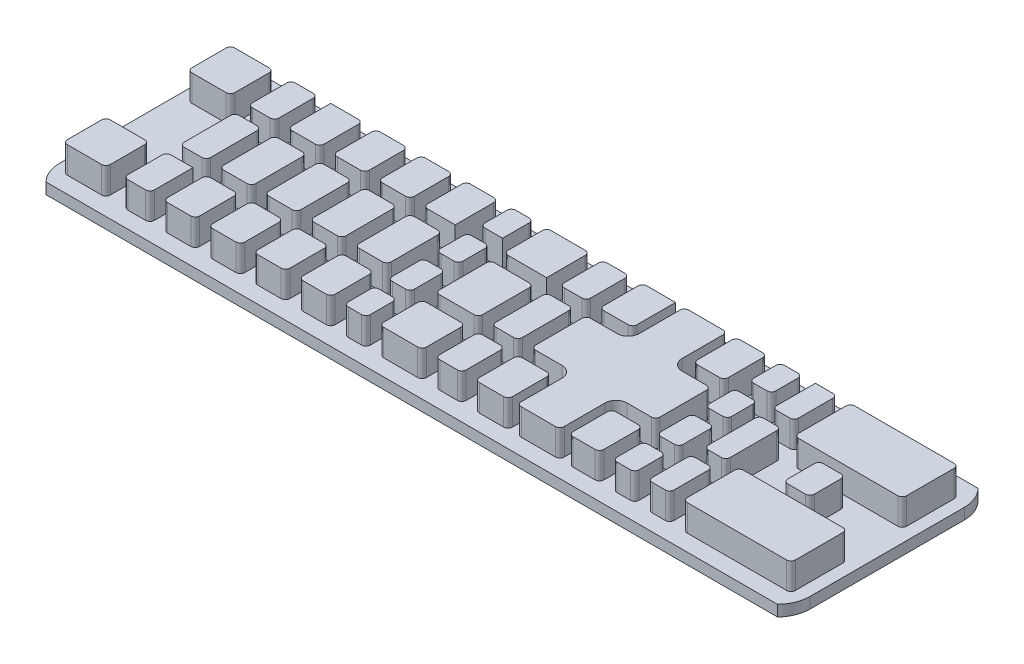
SolidWorks part; units mm, degrees
material "PVB"
ref_plane "Front Plane" through (0, 0, 0) normal (0, 0, 1) x (1, 0, 0)
ref_plane "Top Plane" through (0, 0, 0) normal (0, 1, 0) x (1, 0, 0)
ref_plane "Right Plane" through (0, 0, 0) normal (1, 0, 0) x (0, 0, -1)
ref_axis "X-axis" through (-88.99, 0, 0) along (1, 0, 0)
ref_axis "Y-axis" through (0, 55, 0) along (0, -1, 0)
ref_axis "Z-axis" through (0, 0, -88.99) along (0, 0, 1)
sketch "Sketch1" plane through (0, 0, 0) normal (0, 1, 0) x (1, 0, 0)
  line L1 (109.22, 25.4) -> (-109.22, 25.4)
  line L2 (109.22, 25.4) -> (109.22, -25.4)
  line L3 (109.22, -25.4) -> (-109.22, -25.4)
  line L4 (-109.22, 25.4) -> (-109.22, -25.4)
  line L5 (109.22, 25.4) -> (-109.22, -25.4) construction
  line L6 (109.22, -25.4) -> (-109.22, 25.4) construction
  point P0 (0, 0)
  dimension "D1" = 218.44
  dimension "D2" = 50.8
extrude "Boss-Extrude1" add sketch "Sketch1" along normal blind 2.54
sketch "Sketch4" plane through (0, 2.54, 0) normal (0, 1, 0) x (1, 0, 0)
  line L0 (-99.314, 19.304) -> (-99.314, 9.398)
  line L1 (109.22, 25.4) -> (-109.22, 25.4) construction
  line L2 (-109.22, -25.4) -> (109.22, -25.4) construction
  line L3 (-109.22, 25.4) -> (-109.22, -25.4) construction
  line L4 (-89.408, 19.304) -> (-89.408, 9.398)
  line L5 (-85.344, 19.304) -> (-85.344, 9.398)
  line L6 (-79.248, 19.304) -> (-79.248, 9.398)
  line L7 (-76.2, 19.304) -> (-76.2, 9.398)
  line L8 (-68.834, 19.304) -> (-68.834, 9.398)
  line L9 (-65.786, 19.304) -> (-65.786, 9.398)
  line L10 (-58.42, 19.304) -> (-58.42, 9.398)
  line L11 (-55.372, 19.304) -> (-55.372, 9.398)
  line L12 (-48.006, 19.304) -> (-48.006, 9.398)
  line L13 (-44.958, 19.304) -> (-44.958, 9.398)
  line L14 (-37.592, 19.304) -> (-37.592, 9.398)
  line L15 (-34.544, 19.304) -> (-34.544, 12.192)
  line L16 (35.56, 19.304) -> (35.56, 9.398)
  line L17 (32.512, 19.304) -> (32.512, 12.192)
  line L18 (27.432, 19.304) -> (27.432, 12.192)
  line L19 (24.384, 19.304) -> (24.384, 9.398)
  line L20 (17.272, 19.304) -> (17.272, 9.398)
  line L21 (15.24, 19.304) -> (15.24, 6.35)
  line L22 (5.334, 19.304) -> (5.334, 6.35)
  line L23 (-29.464, 19.304) -> (-29.464, 12.192)
  line L24 (-26.416, 19.304) -> (-26.416, 9.398)
  line L25 (-16.51, 19.304) -> (-16.51, 8.8607)
  line L26 (-13.462, 19.304) -> (-13.462, -6.35)
  line L27 (-7.366, 19.304) -> (-7.366, -6.35)
  line L28 (-4.318, 19.304) -> (-4.318, 9.398)
  line L29 (3.302, 19.304) -> (3.302, 9.398)
  line L30 (-99.314, 19.304) -> (-89.408, 19.304)
  line L31 (-99.314, -19.304) -> (-89.408, -19.304)
  line L32 (-99.314, -9.398) -> (-89.408, -9.398)
  line L33 (-99.314, 9.398) -> (-89.408, 9.398)
  line L34 (-34.544, 9.144) -> (-29.464, 9.144)
  line L35 (-34.544, -9.144) -> (-29.464, -9.144)
  line L36 (-85.344, -19.304) -> (-79.248, -19.304)
  line L37 (-85.344, -9.398) -> (-79.248, -9.398)
  line L38 (-85.344, -6.35) -> (-79.248, -6.35)
  line L39 (-85.344, 9.398) -> (-79.248, 9.398)
  line L40 (-85.344, 6.35) -> (-79.248, 6.35)
  line L41 (-85.344, 19.304) -> (-79.248, 19.304)
  line L42 (-44.958, -19.304) -> (-37.592, -19.304)
  line L43 (-44.958, -9.398) -> (-37.592, -9.398)
  line L44 (-44.958, -6.35) -> (-37.592, -6.35)
  line L45 (-44.958, 6.35) -> (-37.592, 6.35)
  line L46 (-44.958, 9.398) -> (-37.592, 9.398)
  line L47 (-55.372, -19.304) -> (-48.006, -19.304)
  line L48 (-55.372, -9.398) -> (-48.006, -9.398)
  line L49 (-55.372, -6.35) -> (-48.006, -6.35)
  line L50 (-55.372, 6.35) -> (-48.006, 6.35)
  line L51 (-55.372, 9.398) -> (-48.006, 9.398)
  line L52 (-65.786, -19.304) -> (-58.42, -19.304)
  line L53 (-65.786, -9.398) -> (-58.42, -9.398)
  line L54 (-65.786, -6.35) -> (-58.42, -6.35)
  line L55 (-65.786, 6.35) -> (-58.42, 6.35)
  line L56 (-65.786, 9.398) -> (-58.42, 9.398)
  line L57 (-76.2, -19.304) -> (-68.834, -19.304)
  line L58 (-76.2, -9.398) -> (-68.834, -9.398)
  line L59 (-76.2, -6.35) -> (-68.834, -6.35)
  line L60 (-76.2, 6.35) -> (-68.834, 6.35)
  line L61 (-76.2, 9.398) -> (-68.834, 9.398)
  line L62 (-76.2, 19.304) -> (-68.834, 19.304)
  line L63 (-65.786, 19.304) -> (-58.42, 19.304)
  line L64 (-55.372, 19.304) -> (-48.006, 19.304)
  line L65 (-44.958, 19.304) -> (-37.592, 19.304)
  line L66 (-99.314, -9.398) -> (-99.314, -19.304)
  line L67 (-89.408, -9.398) -> (-89.408, -19.304)
  line L68 (-34.544, 12.192) -> (-29.464, 12.192)
  line L69 (-34.544, -1.016) -> (-29.464, -1.016)
  line L70 (-34.544, 2.032) -> (-29.464, 2.032)
  line L71 (-34.544, -12.192) -> (-29.464, -12.192)
  line L72 (-34.544, 19.304) -> (-29.464, 19.304)
  line L73 (-34.544, -19.304) -> (-29.464, -19.304)
  line L74 (-85.344, -9.398) -> (-85.344, -19.304)
  line L75 (-79.248, -9.398) -> (-79.248, -19.304)
  line L76 (-76.2, -9.398) -> (-76.2, -19.304)
  line L77 (-68.834, -9.398) -> (-68.834, -19.304)
  line L78 (-65.786, -9.398) -> (-65.786, -19.304)
  line L79 (-58.42, -9.398) -> (-58.42, -19.304)
  line L80 (-55.372, -9.398) -> (-55.372, -19.304)
  line L81 (-48.006, -9.398) -> (-48.006, -19.304)
  line L82 (-44.958, -9.398) -> (-44.958, -19.304)
  line L83 (-37.592, -9.398) -> (-37.592, -19.304)
  line L84 (-37.592, 6.35) -> (-37.592, -6.35)
  line L85 (-44.958, 6.35) -> (-44.958, -6.35)
  line L86 (-48.006, 6.35) -> (-48.006, -6.35)
  line L87 (-55.372, 6.35) -> (-55.372, -6.35)
  line L88 (-58.42, 6.35) -> (-58.42, -6.35)
  line L89 (-65.786, 6.35) -> (-65.786, -6.35)
  line L90 (-68.834, 6.35) -> (-68.834, -6.35)
  line L91 (-76.2, 6.35) -> (-76.2, -6.35)
  line L92 (-79.248, 6.35) -> (-79.248, -6.35)
  line L93 (-85.344, 6.35) -> (-85.344, -6.35)
  line L94 (-34.544, -12.192) -> (-34.544, -19.304)
  line L95 (-29.464, -12.192) -> (-29.464, -19.304)
  line L96 (-29.464, -1.016) -> (-29.464, -9.144)
  line L97 (-34.544, -1.016) -> (-34.544, -9.144)
  line L98 (-34.544, 9.144) -> (-34.544, 2.032)
  line L99 (-29.464, 9.144) -> (-29.464, 2.032)
  line L100 (-26.416, -19.304) -> (-16.51, -19.304)
  line L101 (-26.416, -9.398) -> (-16.51, -9.398)
  line L102 (-26.416, -6.35) -> (-16.51, -6.35)
  line L103 (-26.416, 6.35) -> (-16.51, 6.35)
  line L104 (-26.416, 9.398) -> (-16.51, 9.398)
  line L105 (-26.416, 19.304) -> (-16.51, 19.304)
  line L106 (-26.416, -9.398) -> (-26.416, -19.304)
  line L107 (-16.51, -9.398) -> (-16.51, -19.304)
  line L108 (-26.416, 6.35) -> (-26.416, -6.35)
  line L109 (-13.462, 19.304) -> (-7.366, 19.304)
  line L110 (-7.366, 19.304) -> (-7.366, 9.398)
  line L111 (-7.366, 9.398) -> (-13.462, 9.398)
  line L112 (-13.462, 9.398) -> (-13.462, 19.304)
  line L113 (-13.462, 6.35) -> (-7.366, 6.35)
  line L114 (-7.366, 6.35) -> (-7.366, -6.35)
  line L115 (-7.366, -6.35) -> (-13.462, -6.35)
  line L116 (-13.462, -6.35) -> (-13.462, 6.35)
  line L117 (-16.51, 6.35) -> (-16.51, -6.35)
  line L118 (-16.51, 9.398) -> (-16.51, 19.304)
  line L119 (-13.462, -9.398) -> (-7.366, -9.398)
  line L120 (-7.366, -9.398) -> (-7.366, -19.304)
  line L121 (-7.366, -19.304) -> (-13.462, -19.304)
  line L122 (-13.462, -19.304) -> (-13.462, -9.398)
  line L123 (-4.318, -19.304) -> (3.302, -19.304)
  line L124 (3.302, -19.304) -> (3.302, -9.398)
  line L125 (3.302, -9.398) -> (-4.318, -9.398)
  line L126 (-4.318, -9.398) -> (-4.318, -19.304)
  line L127 (-4.318, 9.398) -> (3.302, 9.398)
  line L128 (3.302, 9.398) -> (3.302, 19.304)
  line L129 (3.302, 19.304) -> (-4.318, 19.304)
  line L130 (-4.318, 19.304) -> (-4.318, 9.398)
  line L131 (-4.318, 6.35) -> (3.302, 6.35)
  line L132 (-4.318, 6.35) -> (-4.318, -6.35)
  line L133 (-4.318, -6.35) -> (3.302, -6.35)
  line L134 (5.334, -19.304) -> (15.24, -19.304)
  line L135 (15.24, -19.304) -> (15.24, -8.89)
  line L136 (17.78, -6.35) -> (24.384, -6.35)
  line L137 (24.384, -6.35) -> (24.384, 6.35)
  line L138 (24.384, 6.35) -> (17.78, 6.35)
  line L139 (15.24, 8.89) -> (15.24, 19.304)
  line L140 (15.24, 19.304) -> (5.334, 19.304)
  line L141 (5.334, 19.304) -> (5.334, 6.35)
  line L142 (5.334, 6.35) -> (3.302, 6.35)
  line L143 (5.334, -19.304) -> (5.334, -6.35)
  line L144 (5.334, -6.35) -> (3.302, -6.35)
  line L145 (17.272, -19.304) -> (24.384, -19.304)
  line L146 (24.384, -19.304) -> (24.384, -9.398)
  line L147 (24.384, -9.398) -> (17.272, -9.398)
  line L148 (17.272, -9.398) -> (17.272, -19.304)
  line L149 (17.272, 9.398) -> (24.384, 9.398)
  line L150 (24.384, 9.398) -> (24.384, 19.304)
  line L151 (24.384, 19.304) -> (17.272, 19.304)
  line L152 (17.272, 19.304) -> (17.272, 9.398)
  line L153 (40.5638, 19.304) -> (40.5638, 9.398)
  line L154 (43.6118, 19.304) -> (43.6118, 6.35)
  line L155 (35.56, -19.304) -> (40.5638, -19.304)
  line L156 (40.5638, -19.304) -> (40.5638, -9.398)
  line L157 (40.5638, -9.398) -> (35.56, -9.398)
  line L158 (35.56, -9.398) -> (35.56, -19.304)
  line L159 (35.56, -6.35) -> (40.5638, -6.35)
  line L160 (40.5638, -6.35) -> (40.5638, 6.35)
  line L161 (40.5638, 6.35) -> (35.56, 6.35)
  line L162 (35.56, 6.35) -> (35.56, -6.35)
  line L163 (35.56, 19.304) -> (40.5638, 19.304)
  line L164 (40.5638, 19.304) -> (40.5638, 9.398)
  line L165 (40.5638, 9.398) -> (35.56, 9.398)
  line L166 (35.56, 9.398) -> (35.56, 19.304)
  line L167 (27.432, -12.192) -> (32.512, -12.192)
  line L168 (32.512, -12.192) -> (32.512, -19.304)
  line L169 (32.512, -19.304) -> (27.432, -19.304)
  line L170 (27.432, -19.304) -> (27.432, -12.192)
  line L171 (27.432, -9.144) -> (32.512, -9.144)
  line L172 (32.512, -9.144) -> (32.512, -1.016)
  line L173 (32.512, -1.016) -> (27.432, -1.016)
  line L174 (27.432, -1.016) -> (27.432, -9.144)
  line L175 (27.432, 2.032) -> (32.512, 2.032)
  line L176 (32.512, 2.032) -> (32.512, 8.8607)
  line L177 (32.512, 8.8607) -> (27.432, 8.8607)
  line L178 (27.432, 8.8607) -> (27.432, 2.032)
  line L179 (27.432, 12.192) -> (32.512, 12.192)
  line L180 (32.512, 12.192) -> (32.512, 19.304)
  line L181 (32.512, 19.304) -> (27.432, 19.304)
  line L182 (27.432, 19.304) -> (27.432, 12.192)
  line L183 (5.334, -6.35) -> (5.334, -19.304)
  line L184 (3.302, -9.398) -> (3.302, -19.304)
  line L185 (15.24, -6.35) -> (15.24, -19.304)
  line L186 (17.272, -9.398) -> (17.272, -19.304)
  line L187 (-4.318, -9.398) -> (-4.318, -19.304)
  line L188 (-7.366, -9.398) -> (-7.366, -19.304)
  line L189 (-13.462, -9.398) -> (-13.462, -19.304)
  line L190 (-4.318, 6.35) -> (-4.318, -6.35)
  line L191 (24.384, 6.35) -> (24.384, -6.35)
  line L192 (24.384, -9.398) -> (24.384, -19.304)
  line L193 (27.432, 8.8607) -> (27.432, 2.032)
  line L194 (32.512, 8.8607) -> (32.512, 2.032)
  line L195 (27.432, -1.016) -> (27.432, -9.144)
  line L196 (32.512, -1.016) -> (32.512, -9.144)
  line L197 (27.432, -12.192) -> (27.432, -19.304)
  line L198 (32.512, -12.192) -> (32.512, -19.304)
  line L199 (35.56, -9.398) -> (35.56, -19.304)
  line L200 (40.5638, -9.398) -> (40.5638, -19.304)
  line L201 (35.56, 6.35) -> (35.56, -6.35)
  line L202 (40.5638, 6.35) -> (40.5638, -6.35)
  line L203 (43.6118, -19.304) -> (68.5292, -19.304)
  line L205 (43.6118, 19.304) -> (68.5292, 19.304)
  line L206 (68.5292, 6.35) -> (43.6118, 6.35)
  line L207 (43.6118, -6.35) -> (68.5292, -6.35)
  line L208 (51.4858, -3.9841) -> (57.5818, -3.9841)
  line L209 (51.4858, 4.1578) -> (57.5818, 4.1578)
  line L212 (68.5292, 19.304) -> (68.5292, 6.35)
  line L215 (57.5818, 4.1578) -> (57.5818, -3.9841)
  line L216 (51.4858, 4.1578) -> (51.4858, -3.9841)
  line L217 (43.6118, -6.35) -> (43.6118, -19.304)
  line L220 (68.5292, -6.35) -> (68.5292, -19.304)
  arc A0 (17.78, 6.35) -> (15.24, 8.89) centre (17.78, 8.89) cw
  arc A1 (15.24, -8.89) -> (17.78, -6.35) centre (17.78, -8.89) cw
  dimension "D40" = 2.54
  dimension "D41" = 2.54
  dimension "D1" = 9.906
  dimension "D2" = 9.906
  dimension "D3" = 4.064
  dimension "D4" = 6.096
  dimension "D5" = 3.048
  dimension "D6" = 7.366
  dimension "D7" = 3.048
  dimension "D8" = 7.366
  dimension "D9" = 3.048
  dimension "D10" = 7.366
  dimension "D11" = 3.048
  dimension "D12" = 7.366
  dimension "D13" = 3.048
  dimension "D14" = 5.08
  dimension "D15" = 3.048
  dimension "D16" = 9.906
  dimension "D17" = 3.048
  dimension "D18" = 6.096
  dimension "D19" = 3.048
  dimension "D20" = 7.62
  dimension "D21" = 6.096
  dimension "D22" = 6.096
  dimension "D23" = 9.906
  dimension "D24" = 9.906
  dimension "D25" = 7.112
  dimension "D26" = 3.048
  dimension "D27" = 7.112
  dimension "D28" = 3.048
  dimension "D29" = 7.112
  dimension "D30" = 3.048
  dimension "D31" = 2.032
  dimension "D32" = 9.906
  dimension "D33" = 2.032
  dimension "D34" = 7.112
  dimension "D35" = 3.048
  dimension "D36" = 5.08
  dimension "D37" = 3.048
  dimension "D38" = 3.048
  dimension "D39" = 5.0038
  dimension "D42" = 12.954
  dimension "D43" = 12.954
  dimension "D46" = 24.9174
sketch "Sketch5" plane through (0, 2.54, 0) normal (0, 1, 0) x (1, 0, 0)
  line L0 (5.334, 19.304) -> (5.334, 6.35)
  line L1 (-99.314, 9.398) -> (-89.408, 9.398)
  line L2 (-99.314, 9.398) -> (-99.314, 19.304)
  line L3 (-99.314, 19.304) -> (-89.408, 19.304)
  line L4 (-89.408, 9.398) -> (-89.408, 19.304)
  line L5 (-99.314, -19.304) -> (-89.408, -19.304)
  line L6 (-99.314, -19.304) -> (-99.314, -9.398)
  line L7 (-99.314, -9.398) -> (-89.408, -9.398)
  line L8 (-89.408, -19.304) -> (-89.408, -9.398)
  line L9 (-85.344, -19.304) -> (-79.248, -19.304)
  line L10 (-85.344, -19.304) -> (-85.344, -9.398)
  line L11 (-85.344, -9.398) -> (-79.248, -9.398)
  line L12 (-79.248, -19.304) -> (-79.248, -9.398)
  line L13 (-85.344, -6.35) -> (-79.248, -6.35)
  line L14 (-85.344, -6.35) -> (-85.344, 6.35)
  line L15 (-85.344, 6.35) -> (-79.248, 6.35)
  line L16 (-79.248, -6.35) -> (-79.248, 6.35)
  line L17 (-85.344, 9.398) -> (-79.248, 9.398)
  line L18 (-85.344, 9.398) -> (-85.344, 19.304)
  line L19 (-85.344, 19.304) -> (-79.248, 19.304)
  line L20 (-79.248, 9.398) -> (-79.248, 19.304)
  line L21 (-76.2, 9.398) -> (-68.834, 9.398)
  line L22 (-76.2, 9.398) -> (-76.2, 19.304)
  line L23 (-76.2, 19.304) -> (-68.834, 19.304)
  line L24 (-68.834, 9.398) -> (-68.834, 19.304)
  line L25 (-76.2, -6.35) -> (-68.834, -6.35)
  line L26 (-76.2, -6.35) -> (-76.2, 6.35)
  line L27 (-76.2, 6.35) -> (-68.834, 6.35)
  line L28 (-68.834, -6.35) -> (-68.834, 6.35)
  line L29 (-76.2, -19.304) -> (-68.834, -19.304)
  line L30 (-76.2, -19.304) -> (-76.2, -9.398)
  line L31 (-76.2, -9.398) -> (-68.834, -9.398)
  line L32 (-68.834, -19.304) -> (-68.834, -9.398)
  line L33 (-65.786, -19.304) -> (-58.42, -19.304)
  line L34 (-65.786, -19.304) -> (-65.786, -9.398)
  line L35 (-65.786, -9.398) -> (-58.42, -9.398)
  line L36 (-58.42, -19.304) -> (-58.42, -9.398)
  line L37 (-65.786, -6.35) -> (-58.42, -6.35)
  line L38 (-65.786, -6.35) -> (-65.786, 6.35)
  line L39 (-65.786, 6.35) -> (-58.42, 6.35)
  line L40 (-58.42, -6.35) -> (-58.42, 6.35)
  line L41 (-65.786, 9.398) -> (-58.42, 9.398)
  line L42 (-65.786, 9.398) -> (-65.786, 19.304)
  line L43 (-65.786, 19.304) -> (-58.42, 19.304)
  line L44 (-58.42, 9.398) -> (-58.42, 19.304)
  line L45 (-55.372, 9.398) -> (-48.006, 9.398)
  line L46 (-55.372, 9.398) -> (-55.372, 19.304)
  line L47 (-55.372, 19.304) -> (-48.006, 19.304)
  line L48 (-48.006, 9.398) -> (-48.006, 19.304)
  line L49 (-55.372, -6.35) -> (-48.006, -6.35)
  line L50 (-55.372, -6.35) -> (-55.372, 6.35)
  line L51 (-55.372, 6.35) -> (-48.006, 6.35)
  line L52 (-48.006, -6.35) -> (-48.006, 6.35)
  line L53 (-55.372, -19.304) -> (-48.006, -19.304)
  line L54 (-55.372, -19.304) -> (-55.372, -9.398)
  line L55 (-55.372, -9.398) -> (-48.006, -9.398)
  line L56 (-48.006, -19.304) -> (-48.006, -9.398)
  line L57 (-44.958, -19.304) -> (-37.592, -19.304)
  line L58 (-44.958, -19.304) -> (-44.958, -9.398)
  line L59 (-44.958, -9.398) -> (-37.592, -9.398)
  line L60 (-37.592, -19.304) -> (-37.592, -9.398)
  line L61 (-44.958, -6.35) -> (-37.592, -6.35)
  line L62 (-44.958, -6.35) -> (-44.958, 6.35)
  line L63 (-44.958, 6.35) -> (-37.592, 6.35)
  line L64 (-37.592, -6.35) -> (-37.592, 6.35)
  line L65 (-44.958, 9.398) -> (-37.592, 9.398)
  line L66 (-44.958, 9.398) -> (-44.958, 19.304)
  line L67 (-44.958, 19.304) -> (-37.592, 19.304)
  line L68 (-37.592, 9.398) -> (-37.592, 19.304)
  line L69 (-34.544, 12.192) -> (-29.464, 12.192)
  line L70 (-34.544, 12.192) -> (-34.544, 19.304)
  line L71 (-34.544, 19.304) -> (-29.464, 19.304)
  line L72 (-29.464, 12.192) -> (-29.464, 19.304)
  line L73 (-34.544, 2.032) -> (-29.464, 2.032)
  line L74 (-34.544, 2.032) -> (-34.544, 9.144)
  line L75 (-34.544, 9.144) -> (-29.464, 9.144)
  line L76 (-29.464, 2.032) -> (-29.464, 9.144)
  line L77 (-34.544, -9.144) -> (-29.464, -9.144)
  line L78 (-34.544, -9.144) -> (-34.544, -1.016)
  line L79 (-34.544, -1.016) -> (-29.464, -1.016)
  line L80 (-29.464, -9.144) -> (-29.464, -1.016)
  line L81 (-26.416, -6.35) -> (-16.51, -6.35)
  line L82 (-26.416, -6.35) -> (-26.416, 6.35)
  line L83 (-26.416, 6.35) -> (-16.51, 6.35)
  line L84 (-16.51, -6.35) -> (-16.51, 6.35)
  line L85 (-26.416, 9.398) -> (-16.51, 9.398)
  line L86 (-26.416, 9.398) -> (-26.416, 19.304)
  line L87 (-26.416, 19.304) -> (-16.51, 19.304)
  line L88 (-16.51, 9.398) -> (-16.51, 19.304)
  line L89 (-13.462, 9.398) -> (-7.366, 9.398)
  line L90 (-13.462, 9.398) -> (-13.462, 19.304)
  line L91 (-13.462, 19.304) -> (-7.366, 19.304)
  line L92 (-7.366, 9.398) -> (-7.366, 19.304)
  line L93 (-4.318, 9.398) -> (3.302, 9.398)
  line L94 (-4.318, 9.398) -> (-4.318, 19.304)
  line L95 (-4.318, 19.304) -> (3.302, 19.304)
  line L96 (3.302, 9.398) -> (3.302, 19.304)
  line L97 (-13.462, -6.35) -> (-7.366, -6.35)
  line L98 (-13.462, -6.35) -> (-13.462, 6.35)
  line L99 (-13.462, 6.35) -> (-7.366, 6.35)
  line L100 (-7.366, -6.35) -> (-7.366, 6.35)
  line L101 (-34.544, -19.304) -> (-29.464, -19.304)
  line L102 (-34.544, -19.304) -> (-34.544, -12.192)
  line L103 (-34.544, -12.192) -> (-29.464, -12.192)
  line L104 (-29.464, -19.304) -> (-29.464, -12.192)
  line L105 (-26.416, -19.304) -> (-16.51, -19.304)
  line L106 (-26.416, -19.304) -> (-26.416, -9.398)
  line L107 (-26.416, -9.398) -> (-16.51, -9.398)
  line L108 (-16.51, -19.304) -> (-16.51, -9.398)
  line L109 (-13.462, -19.304) -> (-7.366, -19.304)
  line L110 (-13.462, -19.304) -> (-13.462, -9.398)
  line L111 (-13.462, -9.398) -> (-7.366, -9.398)
  line L112 (-7.366, -19.304) -> (-7.366, -9.398)
  line L113 (-4.318, -19.304) -> (3.302, -19.304)
  line L114 (-4.318, -19.304) -> (-4.318, -9.398)
  line L115 (-4.318, -9.398) -> (3.302, -9.398)
  line L116 (3.302, -19.304) -> (3.302, -9.398)
  line L117 (17.272, -19.304) -> (24.384, -19.304)
  line L118 (17.272, -19.304) -> (17.272, -9.398)
  line L119 (17.272, -9.398) -> (24.384, -9.398)
  line L120 (24.384, -19.304) -> (24.384, -9.398)
  line L121 (27.432, -19.304) -> (32.512, -19.304)
  line L122 (27.432, -19.304) -> (27.432, -12.192)
  line L123 (27.432, -12.192) -> (32.512, -12.192)
  line L124 (32.512, -19.304) -> (32.512, -12.192)
  line L125 (35.56, -19.304) -> (40.5638, -19.304)
  line L126 (35.56, -19.304) -> (35.56, -9.398)
  line L127 (35.56, -9.398) -> (40.5638, -9.398)
  line L128 (40.5638, -19.304) -> (40.5638, -9.398)
  line L129 (27.432, -9.144) -> (32.512, -9.144)
  line L130 (27.432, -9.144) -> (27.432, -1.016)
  line L131 (27.432, -1.016) -> (32.512, -1.016)
  line L132 (32.512, -9.144) -> (32.512, -1.016)
  line L133 (27.432, 2.032) -> (32.512, 2.032)
  line L134 (27.432, 2.032) -> (27.432, 8.8607)
  line L135 (27.432, 8.8607) -> (32.512, 8.8607)
  line L136 (32.512, 2.032) -> (32.512, 8.8607)
  line L137 (27.432, 12.192) -> (32.512, 12.192)
  line L138 (27.432, 12.192) -> (27.432, 19.304)
  line L139 (27.432, 19.304) -> (32.512, 19.304)
  line L140 (32.512, 12.192) -> (32.512, 19.304)
  line L141 (17.272, 9.398) -> (24.384, 9.398)
  line L142 (17.272, 9.398) -> (17.272, 19.304)
  line L143 (17.272, 19.304) -> (24.384, 19.304)
  line L144 (24.384, 9.398) -> (24.384, 19.304)
  line L145 (35.56, 9.398) -> (40.5638, 9.398)
  line L146 (35.56, 9.398) -> (35.56, 19.304)
  line L147 (35.56, 19.304) -> (40.5638, 19.304)
  line L148 (40.5638, 9.398) -> (40.5638, 19.304)
  line L149 (35.56, -6.35) -> (40.5638, -6.35)
  line L150 (35.56, -6.35) -> (35.56, 6.35)
  line L151 (35.56, 6.35) -> (40.5638, 6.35)
  line L152 (40.5638, -6.35) -> (40.5638, 6.35)
  line L153 (51.4858, -3.9841) -> (57.5818, -3.9841)
  line L154 (51.4858, -3.9841) -> (51.4858, 4.1578)
  line L155 (51.4858, 4.1578) -> (57.5818, 4.1578)
  line L156 (57.5818, -3.9841) -> (57.5818, 4.1578)
  line L157 (43.6118, -19.304) -> (68.5292, -19.304)
  line L158 (43.6118, -19.304) -> (43.6118, -6.35)
  line L159 (43.6118, -6.35) -> (68.5292, -6.35)
  line L160 (68.5292, -19.304) -> (68.5292, -6.35)
  line L161 (43.6118, 6.35) -> (68.5292, 6.35)
  line L162 (43.6118, 6.35) -> (43.6118, 19.304)
  line L163 (43.6118, 19.304) -> (68.5292, 19.304)
  line L164 (68.5292, 6.35) -> (68.5292, 19.304)
  line L165 (5.334, 6.35) -> (-4.318, 6.35)
  line L166 (-4.318, 6.35) -> (-4.318, -6.35)
  line L167 (-4.318, -6.35) -> (5.334, -6.35)
  line L168 (5.334, -6.35) -> (5.334, -19.304)
  line L169 (5.334, -19.304) -> (15.24, -19.304)
  line L170 (15.24, -19.304) -> (15.24, -8.89)
  line L171 (17.78, -6.35) -> (24.384, -6.35)
  line L172 (24.384, -6.35) -> (24.384, 6.35)
  line L173 (24.384, 6.35) -> (17.78, 6.35)
  line L174 (15.24, 8.89) -> (15.24, 19.304)
  line L175 (15.24, 19.304) -> (5.334, 19.304)
  arc A0 (15.24, -8.89) -> (17.78, -6.35) centre (17.78, -8.89) cw
  arc A1 (17.78, 6.35) -> (15.24, 8.89) centre (17.78, 8.89) cw
extrude "Boss-Extrude4" add sketch "Sketch5" along normal blind 6.096
fillet "Fillet8" radius 2.54 2 edges at (5.334, 5.588, -6.35) (5.334, 5.588, 6.35)
fillet "Fillet9" radius 7.62 4 edges at (-109.22, 1.27, -25.4) (-109.22, 1.27, 25.4) (109.22, 1.27, 25.4) (109.22, 1.27, -25.4)
fillet "Fillet10" radius 1.016 47 edges at (40.5638, 5.588, -6.35) (32.512, 5.588, -8.8607) (32.512, 5.588, -19.304) (40.5638, 5.588, -19.304) (17.272, 5.588, -19.304) (24.384, 5.588, -19.304) (27.432, 5.588, -19.304) (27.432, 5.588, -8.8607) (27.432, 5.588, 1.016) (27.432, 5.588, 12.192) (24.384, 5.588, 9.398) (32.512, 5.588, -12.192) (32.512, 5.588, -2.032) (32.512, 5.588, 1.016) (32.512, 5.588, 12.192) (32.512, 5.588, 9.144) (24.384, 5.588, 19.304) (17.272, 5.588, 19.304) (17.272, 5.588, 9.398) (17.272, 5.588, -9.398) (24.384, 5.588, -9.398) (27.432, 5.588, -12.192) (27.432, 5.588, -2.032) (27.432, 5.588, 9.144) (27.432, 5.588, 19.304) (32.512, 5.588, 19.304) (35.56, 5.588, -6.35) (40.5638, 5.588, -9.398) (35.56, 5.588, -9.398) (35.56, 5.588, 6.35) (35.56, 5.588, 9.398) (35.56, 5.588, 19.304) (40.5638, 5.588, 19.304) (40.5638, 5.588, 6.35) (40.5638, 5.588, 9.398) (43.6118, 5.588, -6.35) (43.6118, 5.588, -19.304) (68.5292, 5.588, -19.304) (68.5292, 5.588, -6.35) (57.5818, 5.588, -4.1578) (51.4858, 5.588, -4.1578) (57.5818, 5.588, 3.9841) (51.4858, 5.588, 3.9841) (43.6118, 5.588, 6.35) (43.6118, 5.588, 19.304) (68.5292, 5.588, 6.35) (68.5292, 5.588, 19.304)
fillet "Fillet11" radius 1.016 118 edges at (-89.408, 5.588, -9.398) (-89.408, 5.588, 9.398) (-99.314, 5.588, -9.398) (-99.314, 5.588, -19.304) (-89.408, 5.588, -19.304) (-85.344, 5.588, -19.304) (-79.248, 5.588, -6.35) (-68.834, 5.588, -6.35) (-65.786, 5.588, -19.304) (-79.248, 5.588, -19.304) (-68.834, 5.588, -19.304) (-58.42, 5.588, -9.398) (-58.42, 5.588, -6.35) (-34.544, 5.588, 9.144) (-58.42, 5.588, 6.35) (-48.006, 5.588, 6.35) (-68.834, 5.588, 9.398) (-68.834, 5.588, 6.35) (-65.786, 5.588, 6.35) (-68.834, 5.588, -9.398) (-65.786, 5.588, -9.398) (-65.786, 5.588, -6.35) (-76.2, 5.588, -6.35) (-76.2, 5.588, -9.398) (-79.248, 5.588, -9.398) (-85.344, 5.588, -9.398) (-85.344, 5.588, -6.35) (-85.344, 5.588, 6.35) (-79.248, 5.588, 6.35) (-76.2, 5.588, 6.35) (-76.2, 5.588, 9.398) (-68.834, 5.588, 19.304) (-76.2, 5.588, 19.304) (-79.248, 5.588, 19.304) (-89.408, 5.588, 19.304) (-85.344, 5.588, 19.304) (-85.344, 5.588, 9.398) (-99.314, 5.588, 9.398) (-99.314, 5.588, 19.304) (-55.372, 5.588, 6.35) (-55.372, 5.588, -6.35) (-55.372, 5.588, -9.398) (-34.544, 5.588, -12.192) (-44.958, 5.588, -9.398) (-44.958, 5.588, 6.35) (3.302, 5.588, -9.398) (-29.464, 5.588, -2.032) (3.302, 5.588, 9.398) (-7.366, 5.588, -9.398) (-7.366, 5.588, -6.35) (-48.006, 5.588, -9.398) (-55.372, 5.588, -19.304) (-58.42, 5.588, -19.304) (-48.006, 5.588, -19.304) (-48.006, 5.588, -6.35) (-37.592, 5.588, 9.398) (-34.544, 5.588, 19.304) (-44.958, 5.588, 19.304) (-65.786, 5.588, 19.304) (-65.786, 5.588, 9.398) (-58.42, 5.588, 9.398) (-55.372, 5.588, 9.398) (-48.006, 5.588, 9.398) (-44.958, 5.588, 9.398) (-34.544, 5.588, -2.032) (-29.464, 5.588, 1.016) (-34.544, 5.588, 1.016) (-34.544, 5.588, 12.192) (-26.416, 5.588, 9.398) (-4.318, 5.588, 9.398) (-13.462, 5.588, 9.398) (-26.416, 5.588, -6.35) (-16.51, 5.588, -6.35) (-13.462, 5.588, -6.35) (-13.462, 5.588, -9.398) (-26.416, 5.588, -9.398) (-29.464, 5.588, -9.144) (-34.544, 5.588, -9.144) (-37.592, 5.588, -6.35) (-44.958, 5.588, -6.35) (-44.958, 5.588, -19.304) (-37.592, 5.588, -19.304) (-34.544, 5.588, -19.304) (-29.464, 5.588, -19.304) (-26.416, 5.588, -19.304) (-16.51, 5.588, -19.304) (-13.462, 5.588, -19.304) (-7.366, 5.588, -19.304) (15.24, 5.588, -19.304) (5.334, 5.588, -19.304) (-4.318, 5.588, -19.304) (-4.318, 5.588, -9.398) (-4.318, 5.588, -6.35) (-16.51, 5.588, 9.398) (-7.366, 5.588, 9.398) (-4.318, 5.588, 6.35) (-7.366, 5.588, 6.35) (-13.462, 5.588, 6.35) (-16.51, 5.588, 6.35) (-26.416, 5.588, 6.35) (-29.464, 5.588, 12.192) (-29.464, 5.588, 9.144) (-37.592, 5.588, 6.35) (-58.42, 5.588, 19.304) (-55.372, 5.588, 19.304) (-48.006, 5.588, 19.304) (-37.592, 5.588, 19.304) (-29.464, 5.588, 19.304) (-26.416, 5.588, 19.304) (-16.51, 5.588, 19.304) (-13.462, 5.588, 19.304) (-7.366, 5.588, 19.304) (-4.318, 5.588, 19.304) (3.302, 5.588, 19.304) (5.334, 5.588, 19.304) (15.24, 5.588, 19.304) (24.384, 5.588, -6.35) (24.384, 5.588, 6.35)
sketch "Sketch10" plane through (0, 0, 0) normal (0, 1, 0) x (1, 0, 0)
  line L1 (101.6, 25.4) -> (109.5326, 25.4)
  line L2 (101.6, 25.4) -> (101.6, -25.397)
  line L3 (101.6, -25.397) -> (109.5326, -25.397)
  line L4 (109.5326, 25.4) -> (109.5326, -25.397)
extrude "Cut-Extrude4" cut sketch "Sketch10" along normal through all
sketch "Sketch11" plane through (0, 0, 0) normal (0, 1, 0) x (1, 0, 0)
  line L1 (-101.6, 25.4) -> (-112.8854, 25.4)
  line L2 (-101.6, 25.4) -> (-101.6, -25.4608)
  line L3 (-101.6, -25.4608) -> (-112.8854, -25.4608)
  line L4 (-112.8854, 25.4) -> (-112.8854, -25.4608)
extrude "Cut-Extrude5" cut sketch "Sketch11" along normal blind 10.16
sketch "Sketch12" plane through (0, 0, 0) normal (0, -1, 0) x (1, 0, 0)
  line L0 (101.6, -25.4) -> (101.6, 25.397) construction
  circle A0 centre (25.4, 0) radius 2.54
  dimension "D1" = 5.08
  dimension "D2" = 76.2
extrude "Cut-Extrude6" cut sketch "Sketch12" against normal blind 1.27
sketch "Sketch15" plane through (0, 0, 0) normal (0, 1, 0) x (1, 0, 0)
  line L0 (101.6, 25.4) -> (-101.6, 25.4) construction
  line L1 (71.4068, 25.4) -> (101.6, 25.4)
  line L2 (71.4068, 25.4) -> (71.4068, -25.397)
  line L3 (71.4068, -25.397) -> (101.6, -25.397)
  line L4 (101.6, 25.4) -> (101.6, -25.397)
extrude "Cut-Extrude9" cut sketch "Sketch15" along normal through all
sketch "Sketch17" plane through (0, 0, 25.4) normal (0, 0, 1) x (1, 0, 0)
  line L0 (-101.6, 2.54) -> (101.6, 2.54) construction
  line L1 (71.4486, 2.54) -> (101.8194, 2.54)
  line L2 (71.4486, 2.54) -> (71.4486, 0)
  line L3 (71.4486, 0) -> (101.8194, 0)
  line L4 (101.8194, 2.54) -> (101.8194, 0)
extrude "Cut-Extrude11" cut sketch "Sketch17" against normal through all
sketch "Sketch18" plane through (0, 0, 25.397) normal (0, 0, -1) x (-1, 0, 0)
  line L1 (-71.4068, 0) -> (-71.4486, 0)
  line L2 (-71.4068, 0) -> (-71.4068, 2.54)
  line L3 (-71.4068, 2.54) -> (-71.4486, 2.54)
  line L4 (-71.4486, 0) -> (-71.4486, 2.54)
extrude "Cut-Extrude12" cut sketch "Sketch18" against normal through all both and the other way through all
fillet "Fillet12" radius 7.62 4 edges at (-101.6, 1.27, 25.4) (-101.6, 1.27, -25.4) (71.4068, 1.27, -25.4) (71.4068, 1.27, 25.4)
sketch "Sketch19" plane through (0, 0, 0) normal (0, 1, 0) x (1, 0, 0)
  line L1 (-101.6, 25.4542) -> (71.4068, 25.4542)
  line L2 (-101.6, 25.4542) -> (-101.6, 23.1682)
  line L3 (-101.6, 23.1682) -> (71.4068, 23.1682)
  line L4 (71.4068, 25.4542) -> (71.4068, 23.1682)
  dimension "D1" = 2.286
extrude "Cut-Extrude14" cut sketch "Sketch19" against normal blind 3.81 and the other way through all
sketch "Sketch20" plane through (0, 0, 0) normal (0, 1, 0) x (1, 0, 0)
  line L0 (71.4068, -17.78) -> (71.4598, -25.4) construction
  line L1 (-101.6, -25.4) -> (71.4598, -25.4)
  line L2 (-101.6, -25.4) -> (-101.6, -23.114)
  line L3 (-101.6, -23.114) -> (71.4598, -23.114)
  line L4 (71.4598, -25.4) -> (71.4598, -23.114)
  dimension "D1" = 2.286
extrude "Cut-Extrude15" cut sketch "Sketch20" along normal through all both and the other way through all
sketch "Sketch21" plane through (0, 0, 0) normal (0, -1, 0) x (1, 0, 0)
  line L0 (71.4068, -17.78) -> (71.4068, 17.78) construction
  line L1 (69.2285, 23.114) -> (-99.4218, 23.114) construction
  circle A0 centre (54.6428, 15.7988) radius 0.381
  dimension "D1" = 0.762
  dimension "D2" = 16.764
  dimension "D3" = 7.3152
extrude "Cut-Extrude16" cut sketch "Sketch21" against normal blind 1.27
mirror "Mirror1" about plane through (0, 0, 0) normal (0, 0, 1) of "Cut-Extrude16"
